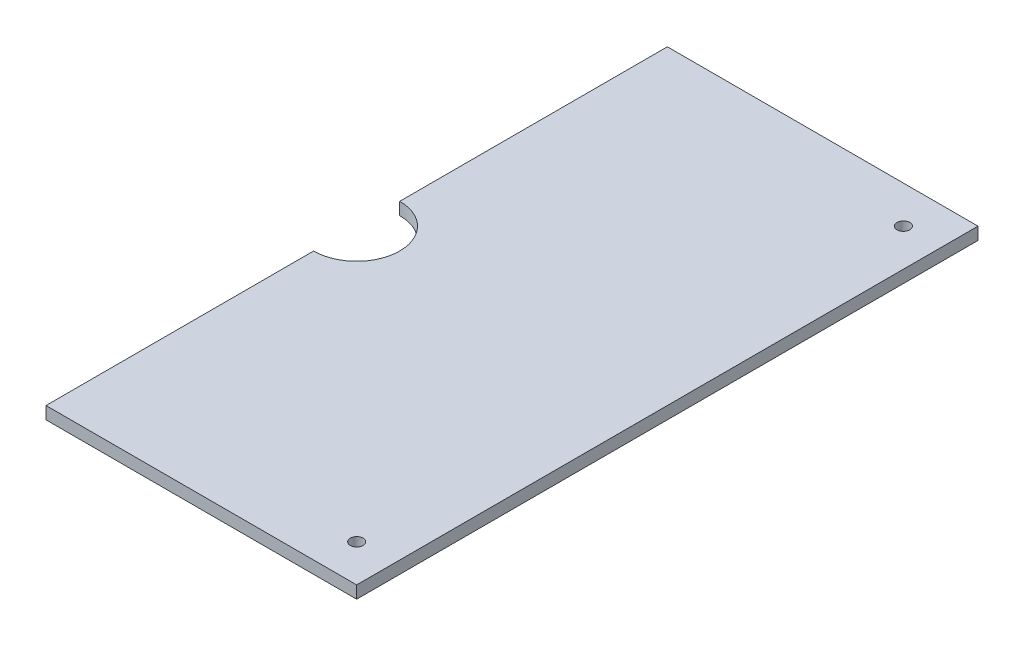
SolidWorks part; units mm, degrees
material "Copper"
ref_plane "Front Plane" through (0, 0, 0) normal (0, 0, 1) x (1, 0, 0)
ref_plane "Top Plane" through (0, 0, 0) normal (0, 1, 0) x (1, 0, 0)
ref_plane "Right Plane" through (0, 0, 0) normal (1, 0, 0) x (0, 0, -1)
sketch "Sketch1" plane through (0, 0, 0) normal (0, 1, 0) x (1, 0, 0)
  line L0 (0, -11) -> (0, -79.375)
  line L1 (0, 79.375) -> (79.37, 79.375)
  line L2 (0, 79.375) -> (0, 11)
  line L3 (0, -79.375) -> (79.37, -79.375)
  line L4 (79.37, 79.375) -> (79.37, -79.375)
  line L5 (0, 0) -> (79.37, 0) construction
  arc A0 (0, -11) -> (0, 11) centre (0, 0) ccw
  circle A1 centre (69.84, 69.845) radius 1.6319
  circle A2 centre (69.84, -69.845) radius 1.6319
  dimension "D1" = 11
  dimension "D4" = 3.2639
  dimension "D2" = 79.37
  dimension "D3" = 158.75
  dimension "D5" = 9.53
  dimension "D6" = 9.53
extrude "Boss-Extrude1" add sketch "Sketch1" along normal blind 3.175
equation "\"D6@Sketch1\"=\"D5@Sketch1\""
